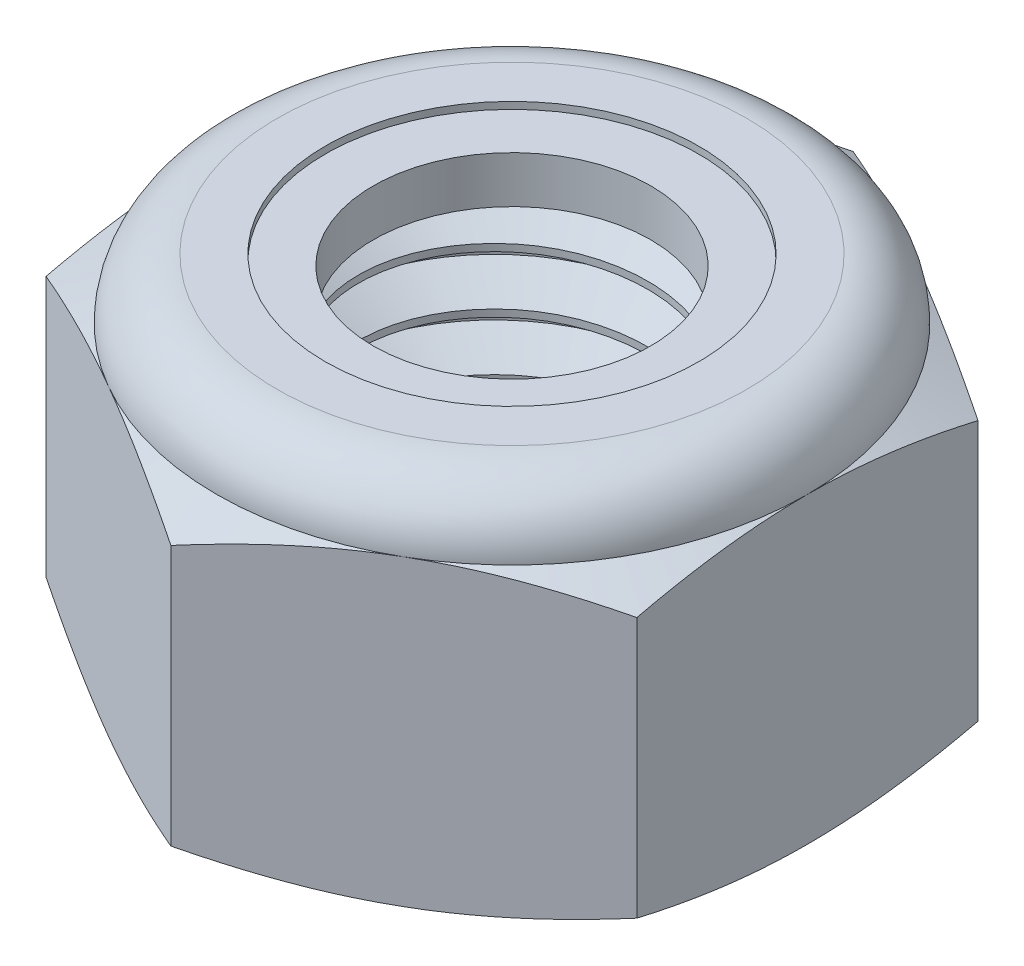
SolidWorks part; units mm, degrees
ref_plane "Front" through (0, 0, 0) normal (0, 0, 1) x (1, 0, 0)
ref_plane "Top" through (0, 0, 0) normal (0, 1, 0) x (1, 0, 0)
ref_plane "Right" through (0, 0, 0) normal (1, 0, 0) x (0, 0, -1)
sketch "Sketch1" plane through (0, 0, 0) normal (0, 1, 0) x (1, 0, 0)
  line L1 (0, 7.5056) -> (-6.5, 3.7528)
  line L2 (-6.5, 3.7528) -> (-6.5, -3.7528)
  line L3 (-6.5, -3.7528) -> (0, -7.5056)
  line L4 (0, -7.5056) -> (6.5, -3.7528)
  line L5 (6.5, -3.7528) -> (6.5, 3.7528)
  line L6 (6.5, 3.7528) -> (0, 7.5056)
  circle A0 centre (0, 0) radius 6.5 construction
  dimension "Hex Flats" = 13
extrude "Extrude1" add sketch "Sketch1" along normal blind 8
sketch "Sketch2" plane through (0, 0, 0) normal (1, 0, 0) x (0, 0, -1)
  line L0 (-4, 0) -> (-4, 8) construction
  line L1 (0, 0) -> (4, 0)
  line L2 (0, 0) -> (0, 8)
  line L3 (0, 8) -> (4, 8)
  line L4 (4, 0) -> (4, 8)
  line L5 (-3.7528, 8) -> (3.7528, 8) construction
  line L7 (0, -4) -> (0, 0) construction
  dimension "Thread Dia" = 8
revolve "Revolve1" add sketch "Sketch2" angle 360 about L7
sketch "Sketch8" plane through (0, 0, 0) normal (0, -1, 0) x (1, 0, 0)
  circle A1 centre (0, 0) radius 4
  circle A2 centre (0, 0) radius 4
  dimension "D1" = 0
curve "Helix/Spiral1" pitch 1.25 height 9.25 turns 7.4 parameters "Pitch"=1.25
sketch "Sketch10" plane through (0, 0, 0) normal (0, -1, 0) x (1, 0, 0)
  circle A1 centre (0, 0) radius 4
  circle A2 centre (0, 0) radius 4
  dimension "D1" = 0
extrude "Boss-Extrude1" add sketch "Sketch10" against normal through all draft 45
sketch "Sketch11" plane through (0, 8, 0) normal (0, 1, 0) x (1, 0, 0)
  circle A1 centre (0, 0) radius 4
  circle A2 centre (0, 0) radius 4
  dimension "D1" = 0
extrude "Boss-Extrude2" add sketch "Sketch11" against normal through all draft 45
sketch "Sketch9" plane through (0, 0, 0) normal (1, 0, 0) x (0, 0, -1)
  line L0 (4, -1.0938) -> (4, 0)
  line L1 (4, -1.0938) -> (3.1881, -0.625)
  line L2 (3.1881, -0.625) -> (3.1881, -0.4688)
  line L3 (3.1881, -0.4688) -> (4, 0)
  line L4 (-4, 0) -> (4, 0) construction
  line L5 (4, -0.5469) -> (3.1881, -0.5469) construction
  line L6 (3.5941, -0.8594) -> (3.5941, -0.2344) construction
  dimension "D1" = 0.1562
  dimension "D2" = 0.625
  dimension "D3" = 60
sweep "Cut-Sweep1" cut profiles "Sketch9" path "Helix/Spiral1"
combine bodies "Combine1" operation type subtract main body 108 bodies to subtract 132
sketch "Sketch5" plane through (0, 0, 0) normal (1, 0, 0) x (0, 0, -1)
  line L0 (0, 0) -> (6.5, 0)
  line L1 (6.5, 0) -> (7.5056, 0.4689)
  line L2 (7.5056, 0.4689) -> (7.5056, 6.1978)
  line L3 (7.5056, 6.1978) -> (6.5, 6.6667)
  line L4 (5.1667, 8) -> (5.1667, 9.27)
  line L5 (5.1667, 9.27) -> (8.7756, 9.27)
  line L6 (8.7756, 9.27) -> (8.7756, -1.27)
  line L7 (8.7756, -1.27) -> (0, -1.27)
  line L8 (0, -1.27) -> (0, 0)
  line L9 (6.5, 6.6667) -> (6.5, 0) construction
  line L10 (0, 0) -> (4, 0) construction
  line L13 (7.5056, 3.3333) -> (8.7756, 3.3333) construction
  line L14 (7.5056, 8) -> (7.5056, 0) construction
  line L15 (0, 0) -> (0, 9.27) construction
  line L20 (0, 9.27) -> (5.1667, 9.27) construction
  line L22 (0, 8) -> (4, 8) construction
  arc A0 (6.5, 6.6667) -> (5.1667, 8) centre (5.1667, 6.6667) ccw
  dimension "D1" = 25
  dimension "D2" = 1.27
  dimension "D3" = 8
  dimension "D4" = 1.3333
revolve "Cut-Revolve3" cut sketch "Sketch5" angle 360 about L15
sketch "Sketch6" plane through (0, 0, 0) normal (1, 0, 0) x (0, 0, -1)
  line L0 (0, 6.6667) -> (6.3476, 6.6667)
  line L1 (5.1667, 7.8476) -> (4.1097, 7.8476)
  line L2 (0, 9.27) -> (0, 6.6667)
  line L3 (4.1097, 9.27) -> (0, 9.27)
  line L4 (0, 9.27) -> (5.1667, 9.27) construction
  line L5 (0, 0) -> (0, 9.27) construction
  line L6 (0, 9.27) -> (0, 0) construction
  line L7 (4.1097, 7.8476) -> (4.1097, 9.27)
  line L8 (5.1667, 8) -> (5.1667, 7.8476) construction
  line L9 (4.1097, 7.8476) -> (3.0528, 7.8476) construction
  line L10 (3.0528, 7.8476) -> (3.0528, 0) construction
  line L13 (3.0528, 7.2969) -> (4, 6.75) construction
  line L15 (4, 0) -> (4, 8) construction
  line L16 (3.0528, 7.4531) -> (4, 8) construction
  line L19 (3.5264, 7.0234) -> (3.5264, 7.7266) construction
  line L20 (3.0528, 7.2969) -> (3.0528, 7.4531) construction
  line L21 (4, 6.75) -> (4, 8) construction
  line L22 (4, 7.375) -> (3.0528, 7.375) construction
  arc A0 (6.3476, 6.6667) -> (5.1667, 7.8476) centre (5.1667, 6.6667) ccw
  arc A1 (6.5, 6.6667) -> (5.1667, 8) centre (5.1667, 6.6667) ccw construction
  dimension "D1" = 0.1524
  dimension "D2" = 1.25
  dimension "D3" = 0.1562
  dimension "D4" = 60
revolve "Cut-Revolve4" cut sketch "Sketch6" angle 360 about L6
sketch "Sketch7" plane through (0, 0, 0) normal (1, 0, 0) x (0, 0, -1)
  line L0 (3.0528, 6.7429) -> (6.2688, 6.7429)
  line L1 (5.1667, 7.7714) -> (3.0528, 7.7714)
  line L2 (3.0528, 7.7714) -> (3.0528, 6.7429)
  line L3 (3.0528, 6.7429) -> (0, 6.7429) construction
  line L4 (0, 6.7429) -> (0, 7.7714) construction
  line L5 (0, 7.7714) -> (3.0528, 7.7714) construction
  line L6 (3.0528, 6.7429) -> (3.0528, 6.6667) construction
  line L7 (0, 6.6667) -> (6.3476, 6.6667) construction
  line L8 (5.1667, 7.7714) -> (5.1667, 7.8476) construction
  line L9 (3.0528, 7.8476) -> (3.0528, 0) construction
  arc A0 (6.2688, 6.7429) -> (5.1667, 7.7714) centre (5.1667, 6.6667) ccw
  arc A2 (6.3476, 6.6667) -> (5.1667, 7.8476) centre (5.1667, 6.6667) ccw construction
  dimension "D1" = 0.0762
revolve "Revolve2" add sketch "Sketch7" angle 360 about L4
move or copy body "Body-Move/Copy1" [suppressed] bodies to move or copy 115 116
equation "\"D4@Sketch5\"=\"Height@Extrude1\"/6"
equation "\"D3@Helix/Spiral1\"=\"Pitch@Helix/Spiral1\"+\"Height@Extrude1\""
equation "\"D1@Sketch9\"=\"Pitch@Helix/Spiral1\"*.125"
equation "\"D2@Sketch9\"=\"Pitch@Helix/Spiral1\"*.50"
equation "\"D2@Sketch6\"=\"Pitch@Helix/Spiral1\""
equation "\"D3@Sketch6\"=\"Pitch@Helix/Spiral1\"/8"
